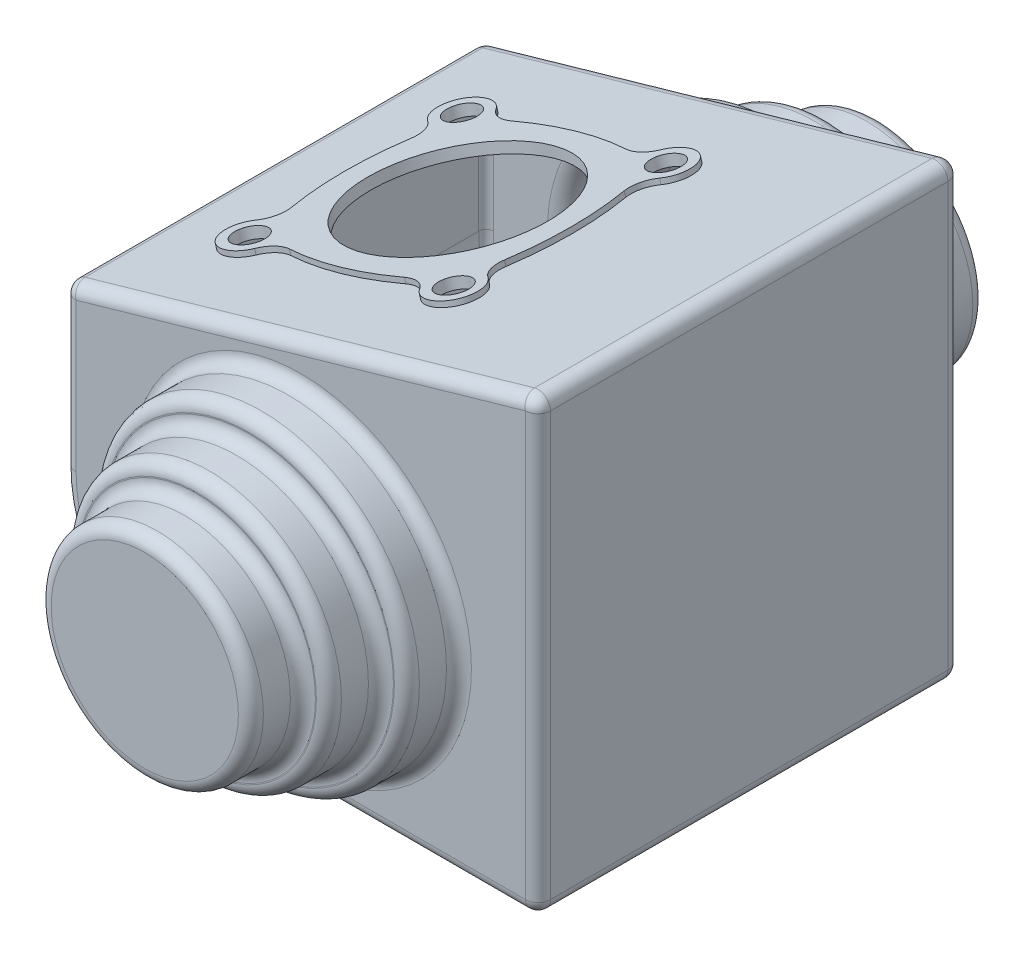
SolidWorks part; units mm, degrees
ref_plane "Front Plane" through (0, 0, 0) normal (0, 0, 1) x (1, 0, 0)
ref_plane "Top Plane" through (0, 0, 0) normal (0, 1, 0) x (1, 0, 0)
ref_plane "Right Plane" through (0, 0, 0) normal (1, 0, 0) x (0, 0, -1)
sketch "Sketch3" plane through (0, 0, 0) normal (0, 0, 1) x (1, 0, 0)
  line L0 (-38, -89) -> (114, -89)
  line L1 (114, -89) -> (114, 128.3779)
  line L2 (114, 128.3779) -> (-114, 63)
  line L3 (-114, 63) -> (-114, -13)
  arc A0 (-114, -13) -> (-38, -89) centre (-38, -13) ccw
  point P6 (-114, -89)
  dimension "D4" = 76
  dimension "D1" = 228
  dimension "D2" = 152
  dimension "D3" = 106
  dimension "D5" = 89
  dimension "D6" = 114
extrude "Boss-Extrude1" add sketch "Sketch3" along normal mid plane 203
sketch "Sketch4" plane through (0, 0, 101.5) normal (0, 0, 1) x (1, 0, 0)
  circle A0 centre (0, 0) radius 76
  circle A1 centre (0, 0) radius 51
  circle A2 centre (0, 0) radius 63.5
  dimension "D1" = 127
  dimension "D2" = 102
  dimension "D3" = 152
extrude "Boss-Extrude3" add sketch "Sketch4" along normal blind 25 contours A0
extrude "Boss-Extrude4" add sketch "Sketch4<4>" along normal blind 50 contours A2
sketch "Sketch4<4>" plane through (0, 0, 101.5) normal (0, 0, 1) x (1, 0, 0) same geometry as "Sketch4"
extrude "Boss-Extrude5" add sketch "Sketch4<5>" along normal blind 75 contours A1
sketch "Sketch4<5>" plane through (0, 0, 101.5) normal (0, 0, 1) x (1, 0, 0) same geometry as "Sketch4"
mirror "Mirror1" about plane through (0, 0, 0) normal (0, 0, 1) of "Boss-Extrude3", "Boss-Extrude4", "Boss-Extrude5"
fillet "Fillet7" radius 6 25 edges at (51, 0, -176.5) (63.5, 0, -151.5) (76, 0, -101.5) (76, 0, -126.5) (51, 0, 176.5) (51, 0, 151.5) (63.5, 0, 151.5) (63.5, 0, 126.5) (76, 0, 126.5) (-91.7401, -66.7401, -101.5) (38, -89, -101.5) (114, 19.689, -101.5) (0, 95.689, -101.5) (-114, 25, -101.5) (-91.7401, -66.7401, 101.5) (38, -89, 101.5) (114, 19.689, 101.5) (-114, 25, 101.5) (-114, 63, 0) (114, 128.3779, 0) (114, -89, 0) (76, 0, 101.5) (-63.5, 0, -126.5) (-51, 0, -151.5) (0, 95.689, 101.5)
shell "Shell1" thickness 2.5
sketch "Sketch5" plane through (-25.3537, 88.4189, 0) normal (-0.2756, 0.9613, 0) x (0.9613, 0.2756, 0)
  line L0 (0, 88.6476) -> (0, 0) construction
  line L1 (0, 0) -> (121.6505, 0) construction
  circle A0 centre (0, 0) radius 45
  arc A1 (57.9955, 41.25) -> (41.25, 57.9955) centre (51, 51) ccw
  arc A2 (-41.25, 57.9955) -> (-57.9955, 41.25) centre (-51, 51) ccw
  arc A3 (-57.9955, -41.25) -> (-41.25, -57.9955) centre (-51, -51) ccw
  arc A4 (41.25, -57.9955) -> (57.9955, -41.25) centre (51, -51) ccw
  arc A6 (-41.25, 57.9955) -> (-28.7806, 53.3033) centre (-31.5, 64.9911) ccw
  arc A7 (41.25, 57.9955) -> (28.7806, 53.3033) centre (31.5, 64.9911) cw
  arc A8 (28.7806, 53.3033) -> (-28.7806, 53.3033) centre (0, -70.3926) ccw
  arc A9 (57.9955, 41.25) -> (53.3033, 28.7806) centre (64.9911, 31.5) ccw
  arc A10 (57.9955, -41.25) -> (53.3033, -28.7806) centre (64.9911, -31.5) cw
  arc A12 (53.3033, -28.7806) -> (53.3033, 28.7806) centre (-70.3926, 0) ccw
  arc A13 (41.25, -57.9955) -> (28.7806, -53.3033) centre (31.5, -64.9911) ccw
  arc A14 (-41.25, -57.9955) -> (-28.7806, -53.3033) centre (-31.5, -64.9911) cw
  arc A15 (28.7806, -53.3033) -> (-28.7806, -53.3033) centre (0, 70.3926) cw
  arc A16 (-57.9955, 41.25) -> (-53.3033, 28.7806) centre (-64.9911, 31.5) cw
  arc A17 (-57.9955, -41.25) -> (-53.3033, -28.7806) centre (-64.9911, -31.5) ccw
  arc A18 (-53.3033, -28.7806) -> (-53.3033, 28.7806) centre (70.3926, 0) cw
  circle A19 centre (-51, 51) radius 7.5
  circle A20 centre (51, 51) radius 7.5
  circle A21 centre (51, -51) radius 7.5
  circle A22 centre (-51, -51) radius 7.5
  dimension "D1" = 90
  dimension "D2" = 24
  dimension "D10" = 24
  dimension "D11" = 63
  dimension "D12" = 24
  dimension "D5" = 127
  dimension "D6" = 15
  dimension "D3" = 51
  dimension "D4" = 51
  dimension "D7" = 102
  dimension "D8" = 102
  dimension "D13" = 63
extrude "Cut-Extrude1" cut sketch "Sketch5" against normal blind 10 contours A0 | A19 | A20 | A21 | A22 region at (-25.3537, 88.4189, 0) region at (-74.3781, 74.3614, -51) region at (23.6706, 102.4764, -51) region at (23.6706, 102.4764, 51) region at (-74.3781, 74.3614, 51)
extrude "Boss-Extrude6" add sketch "Sketch5<4>" along normal blind 2.5
sketch "Sketch5<4>" plane through (-25.3537, 88.4189, 0) normal (-0.2756, 0.9613, 0) x (0.9613, 0.2756, 0) same geometry as "Sketch5"
